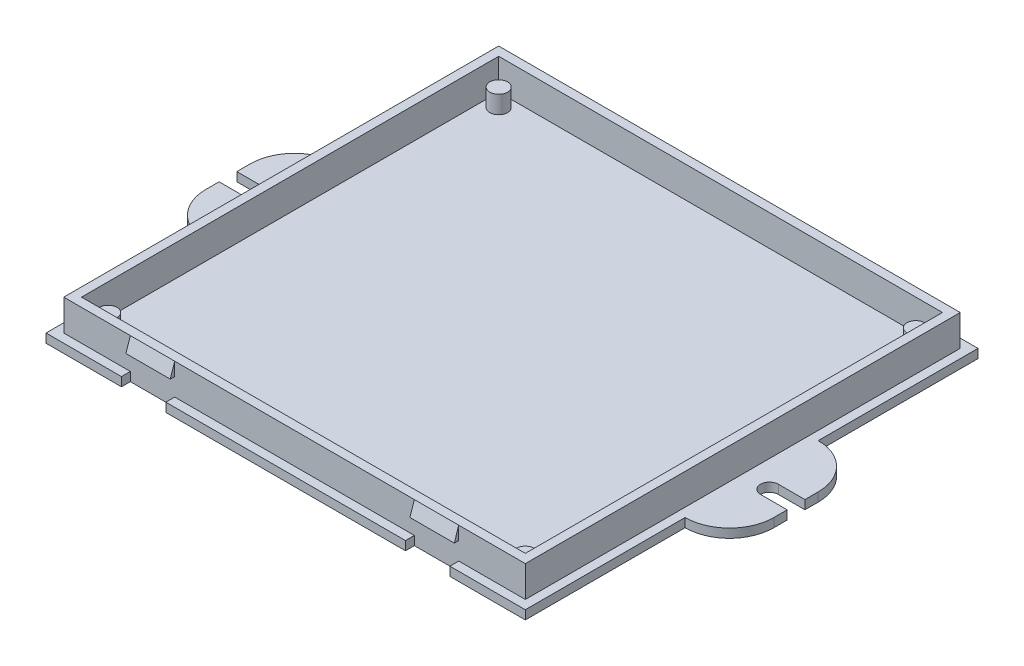
SolidWorks part; units mm, degrees
ref_plane "Front Plane" through (0, 0, 0) normal (0, 0, 1) x (1, 0, 0)
ref_plane "Top Plane" through (0, 0, 0) normal (0, 1, 0) x (1, 0, 0)
ref_plane "Right Plane" through (0, 0, 0) normal (1, 0, 0) x (0, 0, -1)
sketch "Sketch1" plane through (0, 0, 0) normal (0, 1, 0) x (1, 0, 0)
  line L1 (-54, 51) -> (54, 51)
  line L2 (-54, 51) -> (-54, -51)
  line L3 (-54, -51) -> (54, -51)
  line L4 (54, 51) -> (54, -51)
  line L5 (-54, 51) -> (54, -51) construction
  line L6 (-54, -51) -> (54, 51) construction
  point P0 (0, 0)
  dimension "D1" = 102
  dimension "D2" = 108
extrude "Boss-Extrude1" add sketch "Sketch1" along normal blind 2
sketch "Sketch2" plane through (0, 2, 0) normal (0, 1, 0) x (1, 0, 0)
  line L1 (-52, 49) -> (52, 49)
  line L2 (-52, 49) -> (-52, -49)
  line L3 (-52, -49) -> (52, -49)
  line L4 (52, 49) -> (52, -49)
  line L5 (-52, 49) -> (52, -49) construction
  line L6 (-52, -49) -> (52, 49) construction
  point P0 (0, 0)
  dimension "D1" = 98
  dimension "D2" = 104
extrude "Boss-Extrude2" add sketch "Sketch2" along normal blind 7
sketch "Sketch3" plane through (0, 9, 0) normal (0, 1, 0) x (1, 0, 0)
  line L8 (50, -47) -> (50, 47)
  line L9 (50, 47) -> (-50, 47)
  line L10 (-50, 47) -> (-50, -47)
  line L11 (-50, -47) -> (50, -47)
  line L12 (50, -47) -> (50, 47)
  line L13 (50, 47) -> (-50, 47)
  line L14 (-50, 47) -> (-50, -47)
  line L15 (-50, -47) -> (50, -47)
  dimension "D1" = 2
extrude "Cut-Extrude1" cut sketch "Sketch3" against normal blind 7
sketch "Sketch4" plane through (0, 0, 49) normal (0, 0, 1) x (1, 0, 0)
  line L0 (-52, 9) -> (-37, 9)
  line L1 (-52, 9) -> (52, 9) construction
  line L2 (52, 9) -> (32.2553, 9)
  line L4 (-37, 9) -> (-27, 9)
  line L5 (-37, 9) -> (-37, 6)
  line L6 (-37, 6) -> (-27, 6)
  line L7 (-27, 9) -> (-27, 6)
  dimension "D1" = 15
  dimension "D2" = 10
  dimension "D3" = 3
extrude "Boss-Extrude6" add sketch "Sketch4" along normal blind 1 contours L5 L4 L7 L6
sketch "Sketch5" plane through (-27, 0, 0) normal (1, 0, 0) x (0, 0, -1)
  line L0 (-50, 6) -> (-49, 9)
  line L1 (-49, 9) -> (-50, 9)
  line L2 (-50, 9) -> (-50, 5.9638)
  line M2 (-49, 9) -> (-50, 9)
  line M3 (-50, 9) -> (-50, 6)
extrude "Cut-Extrude2" cut sketch "Sketch5" against normal blind 10 contours L0 M3 M2 region at (-27, 8, 49.6667)
sketch "Sketch6" plane through (0, 0, 49) normal (0, 0, 1) x (1, 0, 0)
  line L0 (52, 9) -> (37, 9)
  line L1 (-27, 9) -> (52, 9) construction
  line L3 (37, 9) -> (27, 9)
  line L4 (37, 9) -> (37, 6)
  line L5 (37, 6) -> (27, 6)
  line L6 (27, 9) -> (27, 6)
  dimension "D1" = 15
  dimension "D2" = 10
  dimension "D3" = 3
extrude "Boss-Extrude7" add sketch "Sketch6" along normal blind 1 contours L4 L3 L6 L5
sketch "Sketch7" plane through (37, 0, 0) normal (1, 0, 0) x (0, 0, -1)
  line L0 (-50, 6) -> (-49, 9)
  line L1 (-49, 9) -> (-50, 9)
  line L2 (-50, 9) -> (-50, 6)
extrude "Cut-Extrude3" cut sketch "Sketch7" against normal blind 10
sketch "Sketch9" plane through (0, 0, -49) normal (0, 0, -1) x (-1, 0, 0)
  line L0 (-52, 9) -> (-37, 9)
  line L1 (-52, 9) -> (52, 9) construction
  line L3 (-37, 9) -> (-27, 9)
  line L4 (-37, 9) -> (-37, 6)
  line L5 (-37, 6) -> (-27, 6)
  line L6 (-27, 9) -> (-27, 6)
  dimension "D1" = 15
  dimension "D2" = 10
  dimension "D3" = 3
extrude "Boss-Extrude9" add sketch "Sketch9" along normal blind 1 contours L4 L3 L6 L5
sketch "Sketch10" plane through (27, 0, 0) normal (-1, 0, 0) x (0, 0, 1)
  line L0 (-49, 9) -> (-50, 6)
  line L1 (-50, 6) -> (-50, 9)
  line L2 (-50, 9) -> (-49, 9)
extrude "Cut-Extrude4" cut sketch "Sketch10" against normal blind 10
sketch "Sketch11" plane through (0, 0, -49) normal (0, 0, -1) x (-1, 0, 0)
  line L0 (52, 9) -> (37, 9)
  line L1 (-27, 9) -> (52, 9) construction
  line L3 (37, 9) -> (27, 9)
  line L4 (37, 9) -> (37, 6)
  line L5 (37, 6) -> (27, 6)
  line L6 (27, 9) -> (27, 6)
  dimension "D1" = 15
  dimension "D2" = 10
  dimension "D3" = 3
extrude "Boss-Extrude10" add sketch "Sketch11" along normal blind 1 contours L4 L3 L6 L5
sketch "Sketch12" plane through (-37, 0, 0) normal (-1, 0, 0) x (0, 0, 1)
  line L0 (-49, 9) -> (-50, 6)
  line L1 (-50, 6) -> (-50, 9)
  line L2 (-50, 9) -> (-49, 9)
extrude "Cut-Extrude5" cut sketch "Sketch12" against normal blind 10 contours L2 L0 L1
sketch "Sketch20" plane through (0, 0, 51) normal (0, 0, 1) x (1, 0, 0)
  line L0 (54, 2) -> (37, 2)
  line L1 (-54, 2) -> (54, 2) construction
  line L2 (-54, 0) -> (54, 0) construction
  line L3 (37, 2) -> (27, 2)
  line L4 (37, 2) -> (37, 0)
  line L5 (37, 0) -> (27, 0)
  line L6 (27, 2) -> (27, 0)
  line M6 (-54, 0) -> (54, 0)
  line M8 (54, 2) -> (-54, 2)
  dimension "D1" = 17
  dimension "D2" = 10
extrude "Cut-Extrude7" cut sketch "Sketch20" against normal blind 2 contours L6 L4 M8 M6 region at (32, 1, 51)
sketch "Sketch21" plane through (0, 2, 0) normal (0, 1, 0) x (1, 0, 0)
  line L0 (-52, -49) -> (-37, -49)
  line L1 (-52, -49) -> (27, -49) construction
  line L2 (-54, -51) -> (27, -51) construction
  line L3 (-37, -49) -> (-27, -49)
  line L4 (-37, -49) -> (-37, -51)
  line L5 (-37, -51) -> (-27, -51)
  line L6 (-27, -49) -> (-27, -51)
  dimension "D1" = 15
  dimension "D2" = 10
extrude "Cut-Extrude8" cut sketch "Sketch21" against normal blind 2 contours L4 L3 L6 L5
sketch "Sketch22" plane through (0, 2, 0) normal (0, 1, 0) x (1, 0, 0)
  line L0 (52, 49) -> (37, 49)
  line L1 (52, 49) -> (-52, 49) construction
  line L2 (54, 51) -> (-54, 51) construction
  line L3 (37, 49) -> (27, 49)
  line L4 (37, 49) -> (37, 51)
  line L5 (37, 51) -> (27, 51)
  line L6 (27, 49) -> (27, 51)
  line M6 (-52, 49) -> (52, 49)
  line M12 (54, 51) -> (-54, 51)
  dimension "D1" = 15
  dimension "D2" = 10
extrude "Cut-Extrude9" cut sketch "Sketch22" against normal blind 2 contours L6 L4 M6 M12 region at (32, 2, -50)
sketch "Sketch23" plane through (0, 2, 0) normal (0, 1, 0) x (1, 0, 0)
  line L0 (-52, 49) -> (-37, 49)
  line L1 (27, 49) -> (-52, 49) construction
  line L2 (27, 51) -> (-54, 51) construction
  line L3 (-37, 49) -> (-27, 49)
  line L4 (-37, 49) -> (-37, 51)
  line L5 (-37, 51) -> (-27, 51)
  line L6 (-27, 49) -> (-27, 51)
  dimension "D1" = 15
  dimension "D2" = 10
extrude "Cut-Extrude11" cut sketch "Sketch23" against normal blind 2 contours L4 L3 L6 L5
sketch "Sketch24" plane through (0, 2, 0) normal (0, 1, 0) x (1, 0, 0)
  line L1 (50, 47) -> (47, 47)
  line L2 (50, 47) -> (50, 44)
  line L3 (50, 44) -> (47, 44)
  line L4 (47, 47) -> (47, 44)
  circle A0 centre (47, 44) radius 2
  dimension "D1" = 3
  dimension "D2" = 3
extrude "Boss-Extrude11" add sketch "Sketch24" along normal blind 4 contours A0
sketch "Sketch25" plane through (0, 2, 0) normal (0, 1, 0) x (1, 0, 0)
  line L1 (-50, 47) -> (-47, 47)
  line L2 (-50, 47) -> (-50, 44)
  line L3 (-50, 44) -> (-47, 44)
  line L4 (-47, 47) -> (-47, 44)
  circle A0 centre (-47, 44) radius 2
  dimension "D1" = 3
  dimension "D2" = 3
extrude "Boss-Extrude12" add sketch "Sketch25" along normal blind 4 contours L3 A0 L4 | L4 A0 L3 region at (-46.7171, 2, -43.7171) region at (-47.8488, 2, -44.8488)
sketch "Sketch26" plane through (0, 2, 0) normal (0, 1, 0) x (1, 0, 0)
  line L1 (-50, -47) -> (-47, -47)
  line L2 (-50, -47) -> (-50, -44)
  line L3 (-50, -44) -> (-47, -44)
  line L4 (-47, -47) -> (-47, -44)
  circle A0 centre (-47, -44) radius 2
  dimension "D1" = 3
  dimension "D2" = 3
extrude "Boss-Extrude13" add sketch "Sketch26" along normal blind 4 contours L3 A0 L4 | L4 A0 L3 region at (-47.8488, 2, 44.8488) region at (-46.7171, 2, 43.7171)
sketch "Sketch27" plane through (0, 2, 0) normal (0, 1, 0) x (1, 0, 0)
  line L1 (50, -47) -> (47, -47)
  line L2 (50, -47) -> (50, -44)
  line L3 (50, -44) -> (47, -44)
  line L4 (47, -47) -> (47, -44)
  circle A0 centre (47, -44) radius 2
  dimension "D1" = 3
  dimension "D2" = 3
extrude "Boss-Extrude14" add sketch "Sketch27" along normal blind 4 contours L4 A0 L3 | L3 A0 L4 region at (46.7171, 2, 43.7171) region at (47.8488, 2, 44.8488)
sketch "Sketch28" plane through (-54, 0, 0) normal (-1, 0, 0) x (0, 0, 1)
  line L0 (-51, 1) -> (51, 1)
  line L1 (-51, 2) -> (-51, 0) construction
  line L2 (51, 2) -> (51, 0) construction
  line L3 (-51, 0) -> (51, 0) construction
  line L4 (-15, 2) -> (15, 2)
  line L5 (-15, 2) -> (-15, 0)
  line L6 (-15, 0) -> (15, 0)
  line L7 (15, 2) -> (15, 0)
  line L8 (-15, 2) -> (15, 0) construction
  line L9 (-15, 0) -> (15, 2) construction
  point P7 (0, 1)
  dimension "D1" = 30
extrude "Boss-Extrude15" add sketch "Sketch28" along normal blind 10 contours L6 L7 L4 L5
sketch "Sketch29" plane through (0, 2, 0) normal (0, 1, 0) x (1, 0, 0)
  line L0 (-64, 2) -> (-64, -2)
  line L1 (-64, 15) -> (-64, -15) construction
  line L3 (-64, 2) -> (-58, 2)
  line L4 (-64, 2) -> (-64, -2)
  line L5 (-64, -2) -> (-58, -2)
  line L6 (-58, 2) -> (-58, -2)
  circle A0 centre (-58, 0) radius 2
  point P5 (-64, 0)
  point P9 (0, 0)
  dimension "D1" = 4
  dimension "D2" = 6
extrude "Cut-Extrude12" cut sketch "Sketch29" against normal blind 2 contours L6 A0 | L4 L3 L6 L5 region at (-57.1512, 2, 0)
fillet "Fillet1" radius 10 2 edges at (-64, 1, 15) (-64, 1, -15)
sketch "Sketch30" plane through (54, 0, 0) normal (1, 0, 0) x (0, 0, -1)
  line L0 (-51, 1) -> (51, 1)
  line L1 (-51, 2) -> (-51, 0) construction
  line L2 (51, 2) -> (51, 0) construction
  line L3 (-51, 0) -> (51, 0) construction
  line L4 (-15, 2) -> (15, 2)
  line L5 (-15, 2) -> (-15, 0)
  line L6 (-15, 0) -> (15, 0)
  line L7 (15, 2) -> (15, 0)
  line L8 (-15, 2) -> (15, 0) construction
  line L9 (-15, 0) -> (15, 2) construction
  point P6 (0, 1)
  line M2 (-51, 0) -> (51, 0)
  line M4 (51, 2) -> (-51, 2)
  dimension "D1" = 30
extrude "Boss-Extrude16" add sketch "Sketch30" along normal blind 10 contours L7 L5 L0 M4 | L7 L0 L5 M2 region at (54, 1.5, 0) region at (54, 0.5, 0)
sketch "Sketch32" plane through (0, 2, 0) normal (0, 1, 0) x (1, 0, 0)
  line L0 (64, -2) -> (64, 2)
  line L1 (64, 15) -> (64, -15) construction
  line L3 (64, -2) -> (58, -2)
  line L4 (64, -2) -> (64, 2)
  line L5 (64, 2) -> (58, 2)
  line L6 (58, -2) -> (58, 2)
  circle A0 centre (58, 0) radius 2
  point P5 (64, 0)
  line M14 (64, -15) -> (64, 15)
  dimension "D1" = 4
  dimension "D2" = 6
extrude "Cut-Extrude13" cut sketch "Sketch32" against normal blind 2 contours A0 L3 L5 M14 | L6 A0 | L6 A0 region at (61.7629, 2, 0) region at (57.1512, 2, 0) region at (58.8488, 2, 0)
fillet "Fillet2" radius 10 2 edges at (64, 1, -15) (64, 1, 15)
